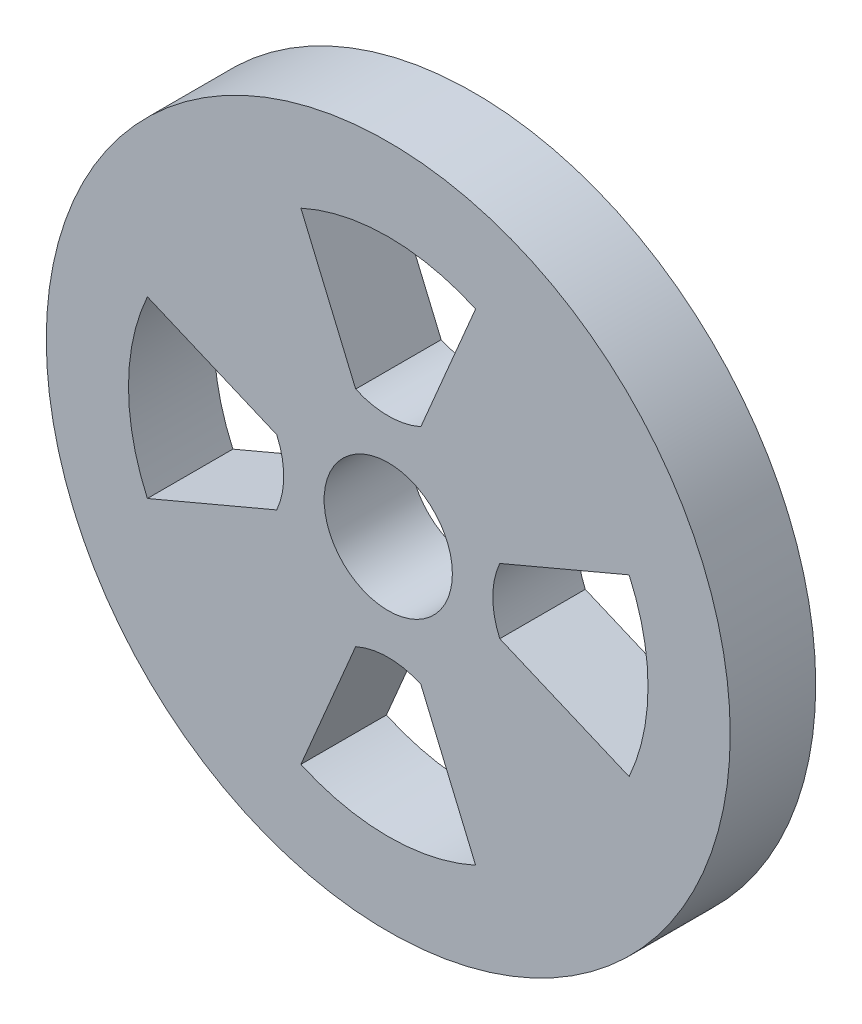
SolidWorks part; units mm, degrees
ref_plane "Piano frontale" through (0, 0, 0) normal (0, 0, 1) x (1, 0, 0)
ref_plane "Piano superiore" through (0, 0, 0) normal (0, 1, 0) x (1, 0, 0)
ref_plane "Piano destro" through (0, 0, 0) normal (1, 0, 0) x (0, 0, -1)
sketch "Schizzo1" plane through (0, 0, 0) normal (0, 0, 1) x (1, 0, 0)
  circle A0 centre (0, 0) radius 80
  circle A1 centre (0, 0) radius 15
extrude "Estrusione-Estrusione1" add sketch "Schizzo1" along normal mid plane 20
sketch "Schizzo2" plane through (0, 0, 10) normal (0, 0, 1) x (1, 0, 0)
  line L0 (-20.4333, 56.3439) -> (-7.6244, 26.0891)
  line L1 (20.4333, 56.3439) -> (7.6244, 26.0891)
  line L2 (56.3439, -20.4333) -> (26.0891, -7.6244)
  line L3 (56.3439, 20.4333) -> (26.0891, 7.6244)
  line L4 (-20.4333, -56.3439) -> (-7.6244, -26.0891)
  line L5 (20.4333, -56.3439) -> (7.6244, -26.0891)
  line L6 (-56.3439, 20.4333) -> (-26.0891, 7.6244)
  line L7 (-56.3439, -20.4333) -> (-26.0891, -7.6244)
  arc A0 (-20.4333, 56.3439) -> (20.4333, 56.3439) centre (0, 11.3557) cw
  arc A1 (-7.6244, 26.0891) -> (7.6244, 26.0891) centre (0, 42.9964) ccw
  arc A2 (26.0891, 7.6244) -> (26.0891, -7.6244) centre (42.9964, 0) ccw
  arc A3 (56.3439, 20.4333) -> (56.3439, -20.4333) centre (11.3557, 0) cw
  arc A4 (7.6244, -26.0891) -> (-7.6244, -26.0891) centre (0, -42.9964) ccw
  arc A5 (20.4333, -56.3439) -> (-20.4333, -56.3439) centre (0, -11.3557) cw
  arc A6 (-26.0891, -7.6244) -> (-26.0891, 7.6244) centre (-42.9964, 0) ccw
  arc A7 (-56.3439, -20.4333) -> (-56.3439, 20.4333) centre (-11.3557, 0) cw
  point P26 (0, 0)
  dimension "D1" = 32.8546
  dimension "D2" = 4
extrude "Taglio-Estrusione1" cut sketch "Schizzo2" against normal through all
